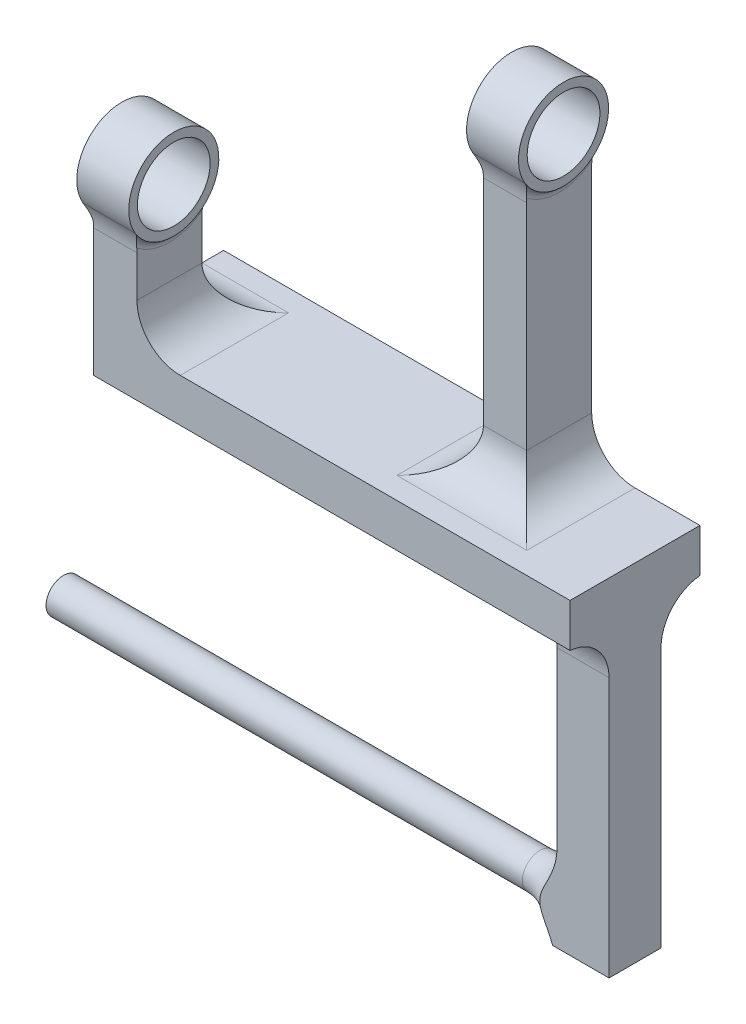
SolidWorks part; units mm, degrees
material "PLA"
ref_plane "Front Plane" through (0, 0, 0) normal (0, 0, 1) x (1, 0, 0)
ref_plane "Top Plane" through (0, 0, 0) normal (0, 1, 0) x (1, 0, 0)
ref_plane "Right Plane" through (0, 0, 0) normal (1, 0, 0) x (0, 0, -1)
sketch "Sketch2" plane through (0, 0, 0) normal (0, 1, 0) x (1, 0, 0)
  line L61 (-60, -15) -> (50, -15)
  line L62 (-60, -15) -> (-60, 15)
  line L63 (-60, 15) -> (50, 15)
  line L64 (50, -15) -> (50, 15)
  dimension "D1" = 30
  dimension "D2" = 110
  dimension "D3" = 60
  dimension "D4" = 15
extrude "Boss-Extrude2" add sketch "Sketch2" along normal blind 10
sketch "Sketch15" plane through (0, 10, 0) normal (0, 1, 0) x (1, 0, 0)
  line L5 (-60, -15) -> (50, -15) construction
  line L6 (-60, -15) -> (-50, -15)
  line L7 (-60, -15) -> (-60, 0)
  line L8 (-60, 0) -> (-50, 0)
  line L9 (-50, -15) -> (-50, 0)
  line L11 (-60, 15) -> (-60, -15) construction
  dimension "D1" = 0
  dimension "D2" = 10
  dimension "D4" = 15
extrude "Boss-Extrude9" add sketch "Sketch15" along normal blind 30
ref_plane "Plane6" through (-55, 0, 0) normal (-1, 0, 0) x (0, 0, 1)
sketch "Sketch17" plane through (-55, 0, 0) normal (-1, 0, 0) x (0, 0, 1)
  line L0 (0, 40) -> (15, 40) construction
  circle A0 centre (7.5, 40) radius 8.4
  dimension "D1" = 16.8
extrude "Extrude-Thin3" add sketch "Sketch17" along normal mid plane 12 thin thin type one direction wall 2
extrude "Cut-Extrude4" cut sketch "Sketch17<2>" against normal mid plane 12
sketch "Sketch17<2>" plane through (-55, 0, 0) normal (-1, 0, 0) x (0, 0, 1) same geometry as "Sketch17"
sketch "Sketch19" plane through (0, 10, 0) normal (0, 1, 0) x (1, 0, 0)
  line L0 (50, 15) -> (-60, 15) construction
  line L1 (15, 15) -> (25, 15)
  line L2 (15, 15) -> (15, 0)
  line L3 (15, 0) -> (25, 0)
  line L4 (25, 15) -> (25, 0)
  line L5 (50, -15) -> (50, 15) construction
  dimension "D1" = 15
  dimension "D2" = 10
  dimension "D3" = 25
extrude "Boss-Extrude11" add sketch "Sketch19" along normal blind 70
ref_plane "Plane7" through (20, 0, 0) normal (-1, 0, 0) x (0, 0, 1)
sketch "Sketch20" plane through (20, 0, 0) normal (-1, 0, 0) x (0, 0, 1)
  line L0 (-15, 80) -> (0, 80) construction
  circle A0 centre (-7.5, 80) radius 8.4
  dimension "D1" = 16.8
extrude "Extrude-Thin4" add sketch "Sketch20" along normal mid plane 12 thin thin type one direction wall 2
extrude "Cut-Extrude5" cut sketch "Sketch20<2>" against normal mid plane 12
sketch "Sketch20<2>" plane through (20, 0, 0) normal (-1, 0, 0) x (0, 0, 1) same geometry as "Sketch20"
sketch "Sketch21" plane through (0, 0, 0) normal (0, -1, 0) x (1, 0, 0)
  line L0 (50, 15) -> (50, -15) construction
  line L1 (50, -6) -> (38, -6)
  line L2 (50, -6) -> (50, 6)
  line L3 (50, 6) -> (38, 6)
  line L4 (38, -6) -> (38, 6)
  line L5 (-60, 15) -> (50, 15) construction
  dimension "D1" = 12
  dimension "D2" = 12
  dimension "D3" = 9
extrude "Boss-Extrude12" add sketch "Sketch21" along normal blind 70
sketch "Sketch22" plane through (38, 0, 0) normal (-1, 0, 0) x (0, 0, 1)
  line L0 (6, -70) -> (6, 0) construction
  line L1 (6, -70) -> (-6, -70) construction
  circle A0 centre (0, -62.5) radius 4
  dimension "D1" = 8
  dimension "D2" = 6
  dimension "D3" = 7.5
extrude "Boss-Extrude13" add sketch "Sketch22" along normal blind 120
ref_plane "Plane8" through (0, 70, 0) normal (0, 1, 0) x (1, 0, 0)
sketch "Sketch24" plane through (0, 70, 0) normal (0, 1, 0) x (1, 0, 0)
  line L0 (-49, -7.5) -> (0, -7.5) construction
  line L1 (-49, -17.9) -> (-49, 2.9) construction
ref_plane "MatingPlane" through (0, 11.4078, 29.8742) normal (0, 0.3567, 0.9342) x (1, 0, 0)
fillet "Fillet1" radius 10 12 edges at (-55, 32.7951, 15) (-55, 32.7951, 0) (20, 72.7951, -15) (20, 72.7951, 0) (-55, 10, 0) (-50, 10, 7.5) (44, 0, 6) (38, 0, 0) (44, 0, -6) (15, 10, -7.5) (20, 10, 0) (25, 10, -7.5)
fillet "Fillet2" radius 10 1 edges at (38, -62.5, -4)
fillet "Fillet3" radius 2 4 edges at (-60, 29.6, 7.5) (-50, 29.6, 7.5) (15, 69.6, -7.5) (25, 69.6, -7.5)
